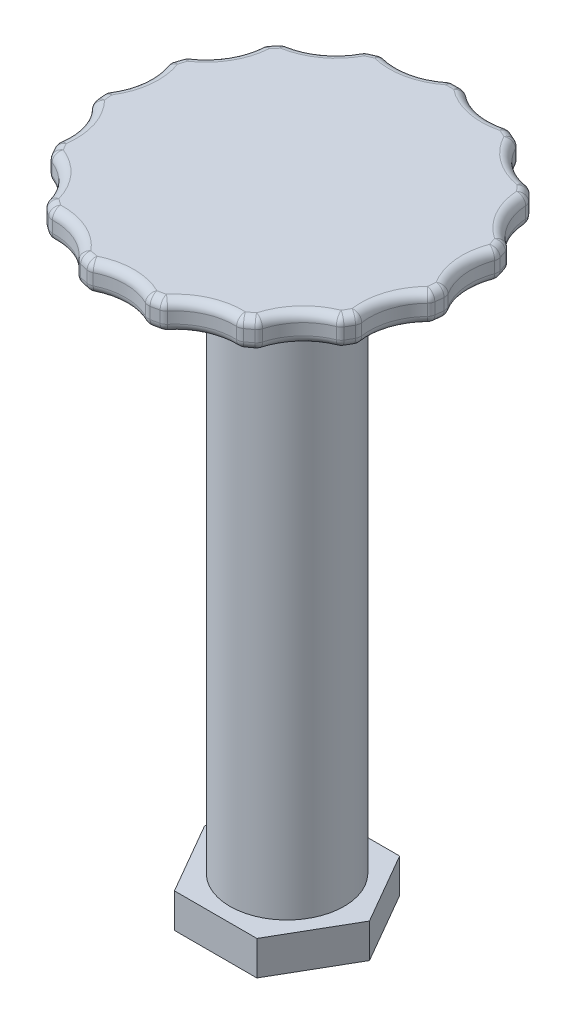
SolidWorks part; units mm, degrees
other "Shaft"
other "Knob"
material "PET"
ref_plane "Front Plane" through (0, 0, 0) normal (0, 0, 1) x (1, 0, 0)
ref_plane "Top Plane" through (0, 0, 0) normal (0, 1, 0) x (1, 0, 0)
ref_plane "Right Plane" through (0, 0, 0) normal (1, 0, 0) x (0, 0, -1)
sketch "Sketch1" plane through (0, 0, 0) normal (0, 1, 0) x (1, 0, 0)
  line L1 (9.1654, -15.875) -> (18.3309, 0)
  line L2 (18.3309, 0) -> (9.1654, 15.875)
  line L3 (9.1654, 15.875) -> (-9.1654, 15.875)
  line L4 (-9.1654, 15.875) -> (-18.3309, 0)
  line L5 (-18.3309, 0) -> (-9.1654, -15.875)
  line L6 (-9.1654, -15.875) -> (9.1654, -15.875)
  circle A0 centre (0, 0) radius 15.875 construction
  dimension "D1" = 31.75
extrude "Key" add sketch "Sketch1" along normal blind 7.62
sketch "Sketch2" plane through (0, 7.62, 0) normal (0, 1, 0) x (1, 0, 0)
  circle A0 centre (0, 0) radius 12.7
  dimension "D1" = 25.4
extrude "Shaft and Weight Holder" add sketch "Sketch2" along normal blind 127 separate body
sketch "Sketch4" plane through (0, 134.62, 0) normal (0, 1, 0) x (1, 0, 0)
  line L0 (0, -49.1485) -> (0, -35.9405) construction
  line L1 (0, -35.9405) -> (0, 0) construction
  circle A0 centre (0, 0) radius 38.1
  arc A1 (-6.35, -37.5671) -> (6.35, -37.5671) centre (0, -49.1485) cw
  arc A2 (-21.0809, -31.7365) -> (-9.4789, -36.902) centre (-19.9905, -44.8994) cw
  arc A3 (-32.1668, -20.4183) -> (-23.6688, -29.8563) centre (-36.5245, -32.8868) cw
  arc A4 (-37.6907, -5.5697) -> (-33.7662, -17.6481) centre (-46.743, -15.1877) cw
  arc A5 (-36.6976, 10.242) -> (-38.0251, -2.3884) centre (-48.8793, 5.1374) cw
  arc A6 (-29.3591, 24.2828) -> (-35.7091, 13.2843) centre (-42.5639, 24.5743) cw
  arc A7 (-16.9441, 34.1249) -> (-27.2186, 26.66) centre (-28.8888, 39.762) cw
  arc A8 (-1.5994, 38.0664) -> (-14.0219, 35.4259) centre (-10.2185, 48.0745) cw
  arc A9 (14.0219, 35.4259) -> (1.5994, 38.0664) centre (10.2185, 48.0745) cw
  arc A10 (27.2186, 26.66) -> (16.9441, 34.1249) centre (28.8888, 39.762) cw
  arc A11 (35.7091, 13.2843) -> (29.3591, 24.2828) centre (42.5639, 24.5743) cw
  arc A12 (38.0251, -2.3884) -> (36.6976, 10.242) centre (48.8793, 5.1374) cw
  arc A13 (33.7662, -17.6481) -> (37.6907, -5.5697) centre (46.743, -15.1877) cw
  arc A14 (23.6688, -29.8563) -> (32.1668, -20.4183) centre (36.5245, -32.8868) cw
  arc A15 (9.4789, -36.902) -> (21.0809, -31.7365) centre (19.9905, -44.8994) cw
  point P19 (0, 0)
  circle M19 centre (0, 0) radius 12.7
  dimension "D1" = 76.2
  dimension "D2" = 12.7
  dimension "D3" = 13.208
  dimension "D4" = 15
extrude "Knob" add sketch "Sketch4" along normal blind 6.35 separate body contours A0 A15 A14 A13 A12 A11 A10 A9 A8 A7 A6 A5 A4 A3 A2 A1 M19 | M19 region at (34.6767, 134.62, -3.6447) region at (0, 134.62, 0)
fillet "Fillet1" radius 1.905 30 edges at (-16.9441, 137.795, -34.1249) (-14.0219, 137.795, -35.4259) (-1.5994, 137.795, -38.0664) (1.5994, 137.795, -38.0664) (14.0219, 137.795, -35.4259) (16.9441, 137.795, -34.1249) (27.2186, 137.795, -26.66) (29.3591, 137.795, -24.2828) (35.7091, 137.795, -13.2843) (36.6976, 137.795, -10.242) (38.0251, 137.795, 2.3884) (37.6907, 137.795, 5.5697) (32.1668, 137.795, 20.4183) (33.7662, 137.795, 17.6481) (23.6688, 137.795, 29.8563) (21.0809, 137.795, 31.7365) (6.35, 137.795, 37.5671) (9.4789, 137.795, 36.902) (-9.4789, 137.795, 36.902) (-6.35, 137.795, 37.5671) (-21.0809, 137.795, 31.7365) (-23.6688, 137.795, 29.8563) (-32.1668, 137.795, 20.4183) (-33.7662, 137.795, 17.6481) (-37.6907, 137.795, 5.5697) (-38.0251, 137.795, 2.3884) (-27.2186, 137.795, -26.66) (-29.3591, 137.795, -24.2828) (-35.7091, 137.795, -13.2843) (-36.6976, 137.795, -10.242)
fillet "Fillet2" radius 1.905 120 edges at (27.1957, 134.62, -26.5516) (28.3138, 134.62, -25.4939) (29.2489, 134.62, -24.2713) (31.1254, 134.62, -17.9703) (35.644, 134.62, -13.1946) (36.2353, 134.62, -11.7735) (36.5922, 134.62, -10.2764) (35.7436, 134.62, -3.7568) (37.9292, 134.62, 2.4439) (37.8913, 134.62, 3.9825) (37.6084, 134.62, 5.4955) (34.1815, 134.62, 11.1062) (33.656, 134.62, 17.6598) (32.9956, 134.62, 19.05) (32.1218, 134.62, 20.3171) (26.709, 134.62, 24.0489) (23.5634, 134.62, 29.8221) (22.3946, 134.62, 30.8235) (21.081, 134.62, 31.6257) (14.6183, 134.62, 32.8333) (9.3965, 134.62, 36.828) (7.9214, 134.62, 37.2674) (6.3952, 134.62, 37.4659) (0, 134.62, 35.9405) (-6.3952, 134.62, 37.4659) (-7.9214, 134.62, 37.2674) (-9.3965, 134.62, 36.828) (-14.6183, 134.62, 32.8333) (-21.081, 134.62, 31.6257) (-22.3946, 134.62, 30.8235) (-23.5634, 134.62, 29.8221) (-26.709, 134.62, 24.0489) (-32.1218, 134.62, 20.3171) (-32.9956, 134.62, 19.05) (-33.656, 134.62, 17.6598) (-34.1815, 134.62, 11.1062) (-37.6084, 134.62, 5.4955) (-37.8913, 134.62, 3.9825) (-37.9292, 134.62, 2.4439) (-35.7436, 134.62, -3.7568) (-36.5922, 134.62, -10.2764) (-36.2353, 134.62, -11.7735) (-35.644, 134.62, -13.1946) (-31.1254, 134.62, -17.9703) (-29.2489, 134.62, -24.2713) (-28.3138, 134.62, -25.4939) (-27.1957, 134.62, -26.5516) (-21.1253, 134.62, -29.0765) (-16.8481, 134.62, -34.0696) (-15.4967, 134.62, -34.8061) (-14.045, 134.62, -35.3176) (-7.4725, 134.62, -35.1551) (-1.5342, 134.62, -37.9769) (0, 134.62, -38.1) (1.5342, 134.62, -37.9769) (7.4725, 134.62, -35.1551) (14.045, 134.62, -35.3176) (15.4967, 134.62, -34.8061) (16.8481, 134.62, -34.0696) (27.1957, 140.97, -26.5516) (28.3138, 140.97, -25.4939) (29.2489, 140.97, -24.2713) (31.1254, 140.97, -17.9703) (35.644, 140.97, -13.1946) (36.2353, 140.97, -11.7735) (36.5922, 140.97, -10.2764) (35.7436, 140.97, -3.7568) (37.9292, 140.97, 2.4439) (37.8913, 140.97, 3.9825) (37.6084, 140.97, 5.4955) (34.1815, 140.97, 11.1062) (33.656, 140.97, 17.6598) (32.9956, 140.97, 19.05) (32.1218, 140.97, 20.3171) (26.709, 140.97, 24.0489) (23.5634, 140.97, 29.8221) (22.3946, 140.97, 30.8235) (21.081, 140.97, 31.6257) (14.6183, 140.97, 32.8333) (9.3965, 140.97, 36.828) (7.9214, 140.97, 37.2674) (6.3952, 140.97, 37.4659) (0, 140.97, 35.9405) (-6.3952, 140.97, 37.4659) (-7.9214, 140.97, 37.2674) (-9.3965, 140.97, 36.828) (-14.6183, 140.97, 32.8333) (-21.081, 140.97, 31.6257) (-22.3946, 140.97, 30.8235) (-23.5634, 140.97, 29.8221) (-26.709, 140.97, 24.0489) (-32.1218, 140.97, 20.3171) (-32.9956, 140.97, 19.05) (-33.656, 140.97, 17.6598) (-34.1815, 140.97, 11.1062) (-37.6084, 140.97, 5.4955) (-37.8913, 140.97, 3.9825) (-37.9292, 140.97, 2.4439) (-35.7436, 140.97, -3.7568) (-36.5922, 140.97, -10.2764) (-36.2353, 140.97, -11.7735) (-35.644, 140.97, -13.1946) (-31.1254, 140.97, -17.9703) (-29.2489, 140.97, -24.2713) (-28.3138, 140.97, -25.4939) (-27.1957, 140.97, -26.5516) (-21.1253, 140.97, -29.0765) (-16.8481, 140.97, -34.0696) (-15.4967, 140.97, -34.8061) (-14.045, 140.97, -35.3176) (-7.4725, 140.97, -35.1551) (-1.5342, 140.97, -37.9769) (0, 140.97, -38.1) (1.5342, 140.97, -37.9769) (7.4725, 140.97, -35.1551) (14.045, 140.97, -35.3176) (15.4967, 140.97, -34.8061) (16.8481, 140.97, -34.0696) (21.1253, 134.62, -29.0765) (21.1253, 140.97, -29.0765)
sketch "Sketch5" plane through (0, 134.62, 0) normal (0, -1, 0) x (1, 0, 0)
  line L1 (-5.715, 5.715) -> (5.715, 5.715)
  line L2 (-5.715, 5.715) -> (-5.715, -5.715)
  line L3 (-5.715, -5.715) -> (5.715, -5.715)
  line L4 (5.715, 5.715) -> (5.715, -5.715)
  line L5 (-5.715, 5.715) -> (5.715, -5.715) construction
  line L6 (-5.715, -5.715) -> (5.715, 5.715) construction
  point P0 (0, 0)
  dimension "D1" = 11.43
extrude "Boss-Extrude1" add sketch "Sketch5" along normal blind 15.24
chamfer "Chamfer1" distance 2.2225 angle 45 4 edges at (0, 134.62, 5.715) (-5.715, 134.62, 0) (0, 134.62, -5.715) (5.715, 134.62, 0)
fillet "Fillet3" radius 1.27 4 edges at (0, 119.38, -5.715) (-5.715, 119.38, 0) (0, 119.38, 5.715) (5.715, 119.38, 0)
sketch "Sketch6" plane through (0, 119.38, 0) normal (0, -1, 0) x (1, 0, 0)
  line L0 (0, 4.445) -> (0, -4.445) construction
  line L1 (4.445, 4.445) -> (-4.445, 4.445) construction
  line L2 (-4.445, -4.445) -> (4.445, -4.445) construction
  circle A0 centre (0, 0) radius 4.445 construction
  point P6 (0, 0)
